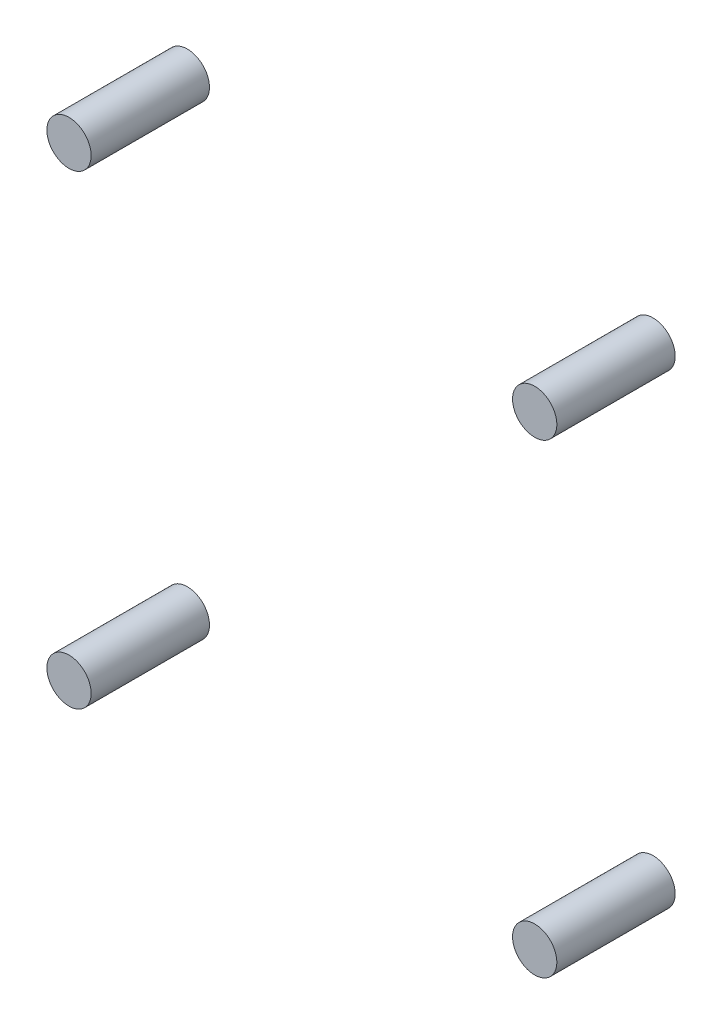
SolidWorks part; units mm, degrees
ref_plane "Front Plane" through (0, 0, 0) normal (0, 0, 1) x (1, 0, 0)
ref_plane "Top Plane" through (0, 0, 0) normal (0, 1, 0) x (1, 0, 0)
ref_plane "Right Plane" through (0, 0, 0) normal (1, 0, 0) x (0, 0, -1)
sketch "Sketch1" plane through (0, 0, 0) normal (0, 0, 1) x (1, 0, 0)
  line L0 (-32.6579, 32.6579) -> (32.6579, -32.6579) construction
  circle A4 centre (32.6579, -32.6579) radius 3.1044
  circle A5 centre (-32.6579, 32.6579) radius 3.1044
  circle A6 centre (-32.6579, -32.6579) radius 3.1044
  circle A7 centre (32.6579, 32.6579) radius 3.1044
  point P21 (0, 0)
  dimension "D1" = 92.3704
extrude "Boss-Extrude1" add sketch "Sketch1" along normal blind 16.6
